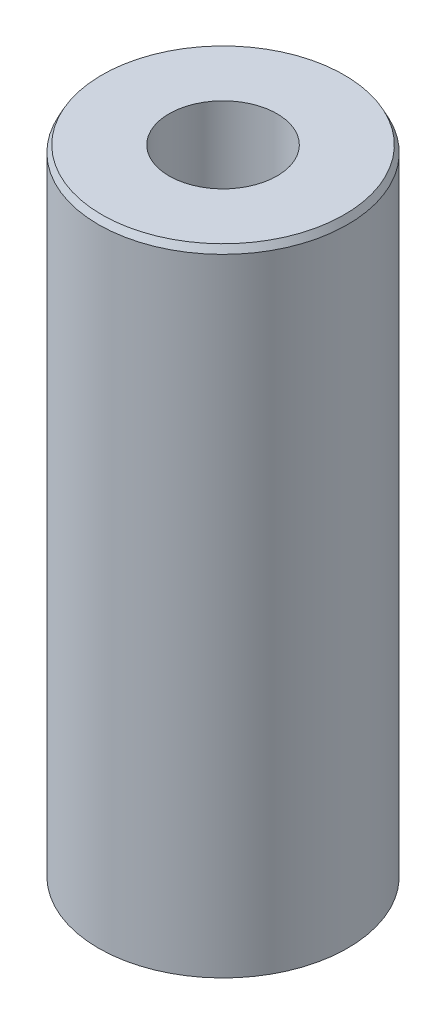
SolidWorks part; units mm, degrees
ref_plane "Front Plane" through (0, 0, 0) normal (0, 0, 1) x (1, 0, 0)
ref_plane "Top Plane" through (0, 0, 0) normal (0, 1, 0) x (1, 0, 0)
ref_plane "Right Plane" through (0, 0, 0) normal (1, 0, 0) x (0, 0, -1)
sketch "Sketch1" plane through (0, 0, 0) normal (0, 1, 0) x (1, 0, 0)
  circle A0 centre (0, 0) radius 17.5
  dimension "SHAFT_OD" = 35
extrude "Boss-Extrude1" add sketch "Sketch1" along normal blind 89.4473
sketch "Sketch2" plane through (0, 0, 0) normal (0, 1, 0) x (1, 0, 0)
  circle A0 centre (0, 0) radius 7.5805
  dimension "BORE_D" = 15.1611
extrude "Cut-Extrude1" cut sketch "Sketch2" along normal through all
chamfer "Chamfer1" distance 0.9494 angle 27.092 2 edges at (0, 89.4473, 17.5) (0, 0, 17.5) first distance on face at (0, 89.4473, 17.5) first distance on face at (0, 0, 7.5805)
